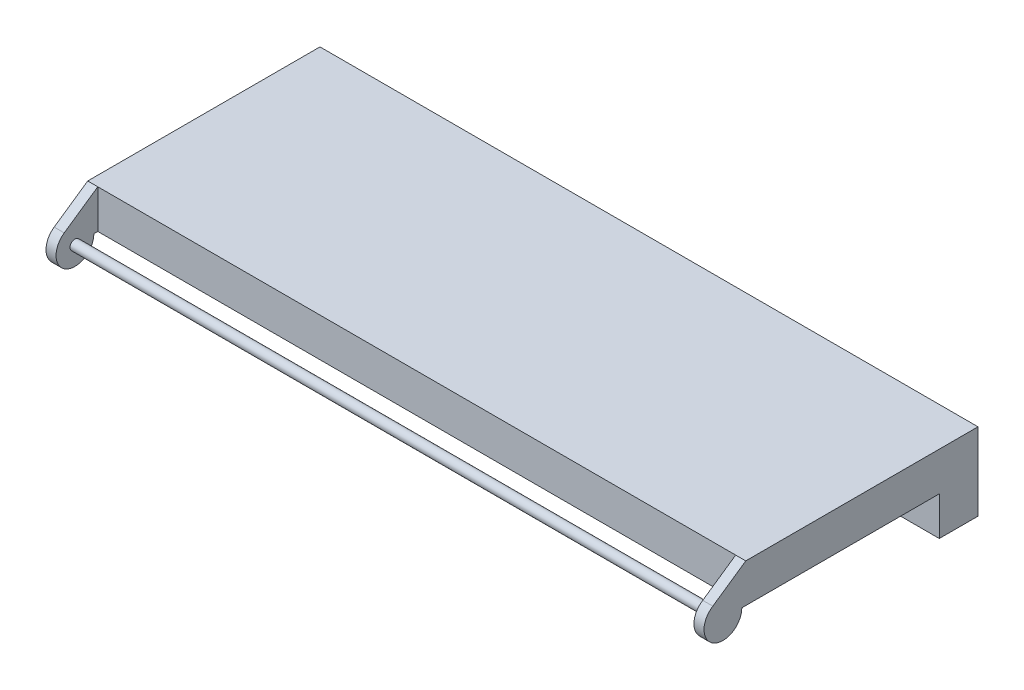
SolidWorks part; units mm, degrees
ref_plane "Front Plane" through (0, 0, 0) normal (0, 0, 1) x (1, 0, 0)
ref_plane "Top Plane" through (0, 0, 0) normal (0, 1, 0) x (1, 0, 0)
ref_plane "Right Plane" through (0, 0, 0) normal (1, 0, 0) x (0, 0, -1)
sketch "Sketch1" plane through (0, 0, 0) normal (0, 1, 0) x (1, 0, 0)
  line L1 (0, 0) -> (85, 0)
  line L2 (0, 0) -> (0, 30)
  line L3 (0, 30) -> (85, 30)
  line L4 (85, 0) -> (85, 30)
  dimension "D1" = 85
  dimension "D2" = 30
extrude "Top surface" add sketch "Sketch1" along normal blind 10
sketch "Sketch6" plane through (0, 0, 0) normal (-1, 0, 0) x (0, 0, 1)
  line L1 (0, 0) -> (-25, 0)
  line L2 (0, 0) -> (0, 5)
  line L3 (0, 5) -> (-25, 5)
  line L4 (-25, 0) -> (-25, 5)
  dimension "D1" = 5
  dimension "D2" = 25
extrude "Top surface cut" cut sketch "Sketch6" against normal through all
sketch "Sketch9" plane through (0, 0, 0) normal (-1, 0, 0) x (0, 0, 1)
  line L0 (0, 5) -> (2.95, 5) construction
  line L1 (4.3357, 7.0083) -> (0, 10)
  line L2 (0.51, 5) -> (0, 5)
  line L3 (0, 10) -> (0, 5) construction
  line L4 (-30, 10) -> (0, 10) construction
  circle A0 centre (2.95, 5) radius 0.64
  circle A1 centre (2.95, 5) radius 1.14
  circle A2 centre (2.95, 5) radius 2.44
  line M5 (0, 5) -> (0, 10)
  dimension "D3" = 0.5
  dimension "D4" = 1.3
  dimension "D1" = 1.28
  dimension "D2" = 2.95
extrude "Boss-Extrude3" add sketch "Sketch9" against normal blind 85 separate body contours A0
sketch "Sketch11" plane through (85, 0, 0) normal (1, 0, 0) x (0, 0, -1)
  line L1 (-2.7863, 13.0835) -> (-2.95, 5) construction
  line L2 (-4.2533, 7.0628) -> (0, 10)
  line L3 (0, 5) -> (-0.51, 5)
  circle A3 centre (-2.95, 5) radius 0.64
  circle A4 centre (-2.95, 5) radius 1.14
  circle A5 centre (-2.95, 5) radius 2.44
  line M14 (0, 10) -> (0, 5)
extrude "Boss-Extrude8" add sketch "Sketch11" against normal blind 1.3 contours L2 L1 A5 L3 M14 | A5 A4 | A4 A3 | L1 L2 A5 region at (85, 7.6945, 0.9671) region at (85, 7.5748, 3.2653) region at (85, 5.7753, 2.1588) region at (85, 6.6595, 1.2566)
extrude "Boss-Extrude9" add sketch "Sketch9<14>" against normal blind 1.3 contours A2 L1 L2 M5 | A2 A1 | A1 A0 region at (0, 7.6901, 1.0572) region at (0, 6.102, 5.0493) region at (0, 5, 1.8422)
sketch "Sketch9<14>" plane through (0, 0, 0) normal (-1, 0, 0) x (0, 0, 1) same geometry as "Sketch9"
